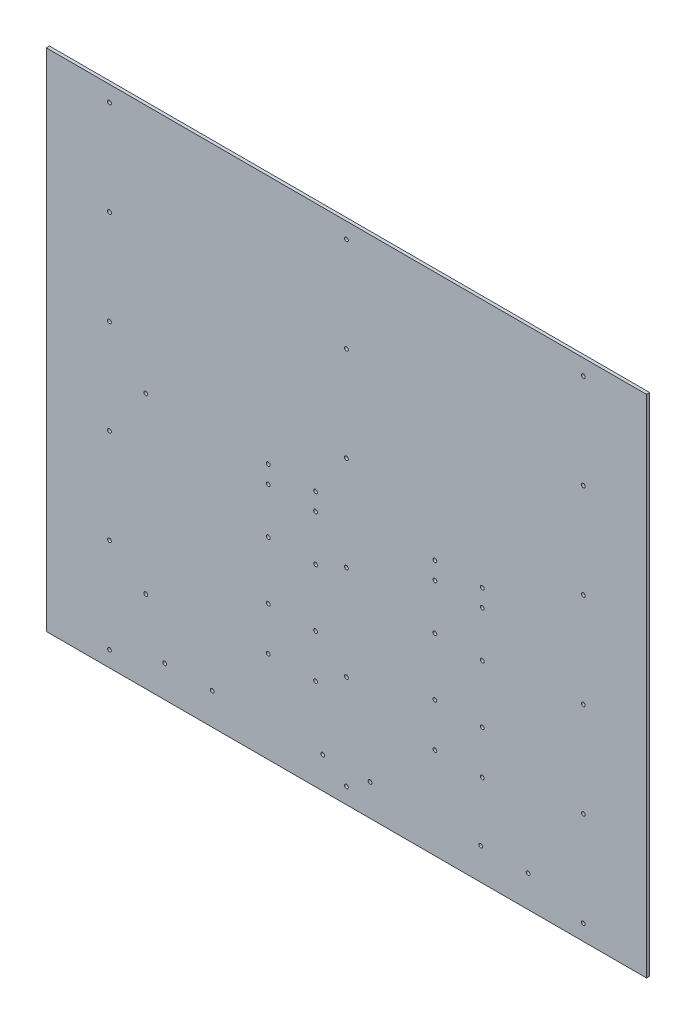
SolidWorks part; units mm, degrees
ref_plane "Płaszczyzna przednia" through (0, 0, 0) normal (0, 0, 1) x (1, 0, 0)
ref_plane "Płaszczyzna górna" through (0, 0, 0) normal (0, 1, 0) x (1, 0, 0)
ref_plane "Płaszczyzna prawa" through (0, 0, 0) normal (1, 0, 0) x (0, 0, -1)
sketch "Szkic1" plane through (0, 0, 0) normal (0, 0, 1) x (1, 0, 0)
  line L1 (-950, -800) -> (950, -800)
  line L2 (-950, -800) -> (-950, 800)
  line L3 (-950, 800) -> (950, 800)
  line L4 (950, -800) -> (950, 800)
  line L5 (-950, -800) -> (950, 800) construction
  line L6 (-950, 800) -> (950, -800) construction
  point P0 (0, 0)
  dimension "D1" = 1900
  dimension "D2" = 1600
extrude "Dodanie-wyciągnięcie1" add sketch "Szkic1" along normal blind 10
hole_wizard "Otwór pod śrubę M101" positions "Szkic2" profile "Szkic3" hole size "M10" standard "Ansi Metric" end condition through all
sketch "Szkic2" plane through (0, 0, 10) normal (0, 0, 1) x (1, 0, 0)
  line L0 (-950, 800) -> (-950, -800) construction
  line L2 (-950, -800) -> (950, -800) construction
  point P0 (-750, -750)
  dimension "D1" = 200
  dimension "D2" = 50
sketch "Szkic3" plane through (-750, -750, 10) normal (1, 0, 0) x (0, -1, 0)
  line L0 (0, 0) -> (0, 10)
  line L1 (0, 10) -> (6, 10)
  line L2 (6, 10) -> (6, 0)
  line L5 (6, 0) -> (0, 0)
  line L11 (0, -6.35) -> (0, 107.95) construction
  dimension "Średnica otworu na wylot" = 12
  dimension "Głębokość otworu na wylot" = 10
pattern_linear "Szyk liniowy1" count 6 spacing 300 along (0, 1, 0) count 3 spacing 750 along (1, 0, 0) of "Otwór pod śrubę M101"
hole_wizard "Otwór pod śrubę M103" positions "Szkic6" profile "Szkic7" hole size "M10" standard "Ansi Metric" end condition through all
sketch "Szkic6" plane through (0, 0, 10) normal (0, 0, 1) x (1, 0, 0)
  line L0 (-950, -800) -> (950, -800) construction
  circle A0 centre (0, -750) radius 6 construction
  point P0 (-75, -700)
  point P2 (75, -700)
  dimension "D1" = 100
  dimension "D2" = 100
  dimension "D3" = 150
  dimension "D4" = 75
sketch "Szkic7" plane through (-75, -700, 10) normal (1, 0, 0) x (0, -1, 0)
  line L0 (0, 0) -> (0, 10)
  line L1 (0, 10) -> (6, 10)
  line L2 (6, 10) -> (6, 0)
  line L5 (6, 0) -> (0, 0)
  line L11 (0, -6.35) -> (0, 107.95) construction
  dimension "Średnica otworu na wylot" = 12
  dimension "Głębokość otworu na wylot" = 10
hole_wizard "Otwór pod śrubę M104" positions "Szkic8" profile "Szkic9" hole size "M10" standard "Ansi Metric" end condition through all
sketch "Szkic8" plane through (0, 0, 10) normal (0, 0, 1) x (1, 0, 0)
  line L0 (-950, -800) -> (950, -800) construction
  circle A0 centre (0, -750) radius 6 construction
  point P0 (-575, -700)
  point P2 (-425, -700)
  point P4 (425, -700)
  point P6 (575, -700)
  dimension "D7" = 575
  dimension "D8" = 575
  dimension "D1" = 100
  dimension "D2" = 100
  dimension "D3" = 100
  dimension "D4" = 100
  dimension "D5" = 150
  dimension "D6" = 150
sketch "Szkic9" plane through (-575, -700, 10) normal (1, 0, 0) x (0, -1, 0)
  line L0 (0, 0) -> (0, 10)
  line L1 (0, 10) -> (6, 10)
  line L2 (6, 10) -> (6, 0)
  line L5 (6, 0) -> (0, 0)
  line L11 (0, -6.35) -> (0, 107.95) construction
  dimension "Średnica otworu na wylot" = 12
  dimension "Głębokość otworu na wylot" = 10
hole_wizard "Otwór pod śrubę M105" positions "Szkic10" profile "Szkic11" hole size "M10" standard "Ansi Metric" end condition through all
sketch "Szkic10" plane through (0, 0, 10) normal (0, 0, 1) x (1, 0, 0)
  point P0 (-635, -540)
  point P3 (-635, 10)
sketch "Szkic11" plane through (-635, -540, 10) normal (1, 0, 0) x (0, -1, 0)
  line L0 (0, 0) -> (0, 10)
  line L1 (0, 10) -> (6, 10)
  line L2 (6, 10) -> (6, 0)
  line L5 (6, 0) -> (0, 0)
  line L11 (0, -6.35) -> (0, 107.95) construction
  dimension "Średnica otworu na wylot" = 12
  dimension "Głębokość otworu na wylot" = 10
hole_wizard "Otwór pod śrubę M106" positions "Szkic12" profile "Szkic13" hole size "M10" standard "Ansi Metric" end condition through all
sketch "Szkic12" plane through (0, 0, 10) normal (0, 0, 1) x (1, 0, 0)
  point P0 (-247.5, -510)
  point P3 (-97.5, -510)
  point P6 (-97.5, -372.5)
  point P9 (-247.5, -372.5)
  point P12 (-97.5, -190)
  point P15 (-247.5, -190)
  point P18 (-247.5, -45)
  point P21 (-97.5, -45)
  point P24 (-97.5, 10)
  point P27 (-247.5, 10)
  point P30 (280, 10)
  point P33 (430, 10)
  point P36 (430, -45)
  point P39 (280, -45)
  point P42 (280, -190)
  point P45 (430, -190)
  point P48 (280, -372.5)
  point P51 (430, -372.5)
  point P54 (430, -510)
  point P57 (280, -510)
sketch "Szkic13" plane through (-247.5, -510, 10) normal (1, 0, 0) x (0, -1, 0)
  line L0 (0, 0) -> (0, 10)
  line L1 (0, 10) -> (6, 10)
  line L2 (6, 10) -> (6, 0)
  line L5 (6, 0) -> (0, 0)
  line L11 (0, -6.35) -> (0, 107.95) construction
  dimension "Średnica otworu na wylot" = 12
  dimension "Głębokość otworu na wylot" = 10
